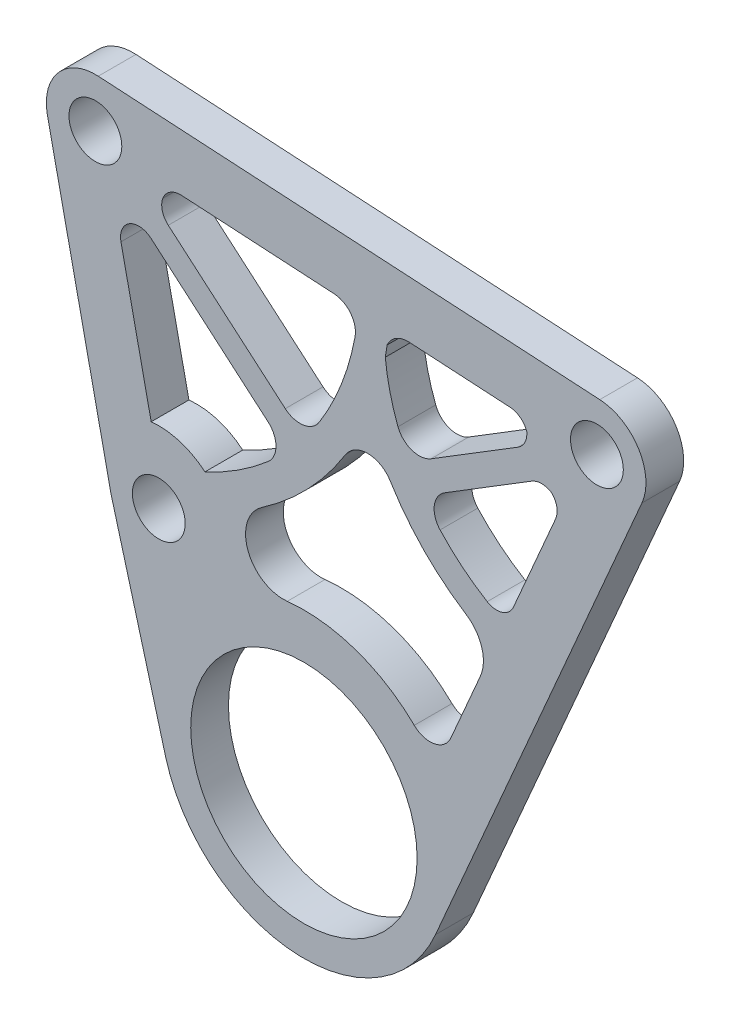
SolidWorks part; units mm, degrees
ref_plane "Front Plane" through (0, 0, 0) normal (0, 0, 1) x (1, 0, 0)
ref_plane "Top Plane" through (0, 0, 0) normal (0, 1, 0) x (1, 0, 0)
ref_plane "Right Plane" through (0, 0, 0) normal (1, 0, 0) x (0, 0, -1)
sketch "Sketch1" plane through (0, 0, 0) normal (0, 0, 1) x (1, 0, 0)
  line L3 (-27.2517, 68.6219) -> (39.2047, 64.735)
  line L4 (-33.9863, 60.7681) -> (-25.5866, 21.66)
  line L7 (-25.5028, 21.3156) -> (-18.3313, -4.9963)
  line L8 (44.7906, 55.6646) -> (17.4374, -7.5457)
  line L9 (-24.3868, 63.4458) -> (35.7559, 59.9282)
  line L10 (-28.4337, 58.7263) -> (-21.3622, 25.8017)
  line L11 (-19.8472, 19.5795) -> (-14.9234, 1.5141)
  line L12 (38.9459, 54.7482) -> (14.9873, -0.6177)
  line L16 (-27.6312, 62.133) -> (0, 0) construction
  circle A0 centre (38.8252, 58.2461) radius 3.5
  circle A1 centre (0, 0) radius 13
  circle A2 centre (-19.2316, 23.0249) radius 3.5
  circle A3 centre (-27.6312, 62.133) radius 3.5
  circle A4 centre (-27.6312, 62.133) radius 6.5
  circle A5 centre (38.8252, 58.2461) radius 6.5
  circle A6 centre (-19.2316, 23.0249) radius 6.5
  circle A7 centre (0, 0) radius 19
  circle A8 centre (0, 0) radius 15
  dimension "D6" = 26
  dimension "D7" = 7
  dimension "D8" = 7
  dimension "D9" = 7
  dimension "D10" = 38
  dimension "D11" = 13
  dimension "D12" = 13
  dimension "D13" = 13
  dimension "D18" = 30
  dimension "D1" = 68
  dimension "D2" = 70
  dimension "D3" = 66.57
  dimension "D4" = 30
  dimension "D5" = 40
  dimension "D14" = 5
  dimension "D15" = 5
  dimension "D16" = 5
  dimension "D17" = 5
extrude "Boss-Extrude2" add sketch "Sketch1" along normal blind 5 contours A5 L3 A4 L9 | A5 L9 A0 L12 | L9 A5 L12 A0 | A3 L16 A4 L9 | L9 A4 L10 A3 | L16 A3 L10 A4 | A6 L10 A4 L4 | A7 L8 A5 L12 | L11 A6 L10 A2 | L10 A6 L11 A2 | A7 L11 A6 L7 | A8 L11 A7 L12 | A7 L16 A8 L12 | L16 A7 L11 A8 | A4 L16 A7 L12 A5 L9 | L16 A4 L10 A6 L11 A7 region at (-23.431, 66.8512, 0) region at (5.8345, 64.2509, 0) region at (43.4213, 62.5812, 0) region at (-27.4669, 41.7122, 0) region at (-23.403, 60.0563, 0) region at (6.823, 41.0913, 0) region at (35.06, 55.9273, 0) region at (-22.9578, 22.1177, 0) region at (-18.5959, 33.0135, 0) region at (-26.8135, 57.1999, 0) region at (29.7136, 26.8388, 0) region at (-20.4113, 10.4427, 0) region at (-15.8467, 28.386, 0) region at (-1.3174, -18.4828, 0) region at (16.1721, 2.9338, 0) region at (-12.1484, 11.0518, 0)
ref_plane "Plane1" through (0, 0, 10.5) normal (0, 0, 1) x (1, 0, 0)
sketch "Sketch6" plane through (0, 0, 0) normal (0, 0, 1) x (1, 0, 0)
  circle A1 centre (0, 0) radius 21
  circle A3 centre (-19.2316, 23.0249) radius 9.5
  circle A5 centre (-27.6312, 62.133) radius 9.5
  circle A7 centre (38.8252, 58.2461) radius 9.5
sketch "Sketch7" plane through (0, 0, 0) normal (0, 0, 1) x (1, 0, 0)
  line L0 (-24.2432, 51.1207) -> (-20.2377, 32.4715)
  line L1 (-27.6312, 62.133) -> (0.6574, 37.8755)
  line L2 (-33.9863, 60.7681) -> (-25.5866, 21.66) construction
  line L3 (-16.231, 60.4645) -> (4.0052, 59.2809)
  line L4 (-27.2517, 68.6219) -> (39.2047, 64.735) construction
  line L5 (33.3489, 48.109) -> (27.7669, 35.2096)
  line L6 (44.7906, 55.6646) -> (17.4374, -7.5457) construction
  line L7 (38.8252, 58.2461) -> (11.4971, 41.4155)
  line L8 (-20.2514, 53.4995) -> (-4.7476, 40.205)
  line L9 (-17.9731, 56.1564) -> (-2.4693, 42.8619)
  line L10 (30.1875, 50.8711) -> (18.6793, 43.7836)
  line L11 (28.3521, 53.8513) -> (16.8439, 46.7637)
  line L12 (13.9417, 58.6998) -> (27.3081, 57.918)
  line L14 (0.6574, 37.8755) -> (1.9745, 36.7461)
  line L15 (23.3701, 25.049) -> (19.4678, 16.0313)
  circle A0 centre (-27.6312, 62.133) radius 9.5 construction
  circle A1 centre (-19.2316, 23.0249) radius 9.5 construction
  circle A2 centre (38.8252, 58.2461) radius 9.5 construction
  arc A6 (-20.2514, 53.4995) -> (-23.0454, 53.8128) centre (-21.8788, 51.6017) ccw
  arc A7 (-23.0454, 53.8128) -> (-24.2432, 51.1207) centre (-21.7989, 51.6457) ccw
  arc A8 (-18.7088, 58.87) -> (-17.9731, 56.1564) centre (-16.3457, 58.0542) ccw
  arc A9 (-16.231, 60.4645) -> (-18.7088, 58.87) centre (-16.3769, 57.9688) ccw
  arc A13 (29.5288, 56.228) -> (27.3081, 57.918) centre (27.1622, 55.4222) ccw
  arc A14 (28.3521, 53.8513) -> (29.5288, 56.228) centre (27.0411, 55.98) ccw
  arc A15 (32.8393, 50.8525) -> (30.1875, 50.8711) centre (31.4985, 48.7424) ccw
  arc A16 (33.3489, 48.109) -> (32.8393, 50.8525) centre (31.0545, 49.1018) ccw
  arc A17 (-13.1084, 30.2883) -> (-4.7382, 35.6584) centre (-27.6312, 62.133) ccw
  arc A18 (2.0256, 43.5461) -> (6.7795, 55.7379) centre (-27.6312, 62.133) ccw
  arc A19 (10.7795, 55.3996) -> (12.4654, 48.2549) centre (38.8252, 58.2461) ccw
  arc A20 (18.0405, 39.2025) -> (24.2876, 34.094) centre (38.8252, 58.2461) ccw
  arc A21 (-13.1084, 30.2883) -> (-20.2377, 32.4715) centre (-19.2316, 23.0249) ccw
  arc A22 (-4.7382, 35.6584) -> (-4.7476, 40.205) centre (-6.7004, 37.9276) ccw
  arc A23 (6.7795, 55.7379) -> (4.0052, 59.2809) centre (3.8301, 56.2861) ccw
  arc A24 (-2.4693, 42.8619) -> (2.0256, 43.5461) centre (-0.5164, 45.1393) ccw
  arc A25 (13.9417, 58.6998) -> (10.7795, 55.3996) centre (13.7664, 55.7027) ccw
  arc A26 (12.4654, 48.2549) -> (16.8439, 46.7637) centre (15.2707, 49.3181) ccw
  arc A27 (18.6793, 43.7836) -> (18.0405, 39.2025) centre (20.2525, 41.2291) ccw
  arc A28 (24.2876, 34.094) -> (27.7669, 35.2096) centre (25.5394, 36.1736) ccw
  arc A29 (-5.5613, 29.9785) -> (5.4838, 41.5323) centre (-27.6312, 62.133) ccw
  arc A33 (-5.5613, 29.9785) -> (-2.2064, 20.8838) centre (-2.7318, 25.8561) ccw
  arc A35 (11.4971, 41.4155) -> (5.4838, 41.5323) centre (8.4557, 39.6835) ccw
  arc A36 (11.442, 41.5088) -> (21.4831, 31.2419) centre (38.8252, 58.2461) ccw
  arc A37 (10.7808, 55.3868) -> (11.0173, 56.9093) centre (-27.6312, 62.133) ccw
  arc A39 (23.3701, 25.049) -> (21.4831, 31.2419) centre (18.7813, 27.0347) ccw
  arc A40 (14.6253, 15.0699) -> (-2.2064, 20.8838) centre (0, 0) ccw
  arc A41 (14.6253, 15.0699) -> (19.4678, 16.0313) centre (16.7146, 17.2227) ccw
  dimension "D10" = 5
  dimension "D11" = 5
  dimension "D12" = 5
  dimension "D13" = 1.75
  dimension "D14" = 1.75
  dimension "D15" = 35
  dimension "D16" = 4
  dimension "D18" = 39
  dimension "D19" = 4
  dimension "D20" = 5
  dimension "D21" = 7
  dimension "D22" = 28.1897
  dimension "D1" = 7.5
  dimension "D2" = 7.5
  dimension "D3" = 7.5
  dimension "D4" = 74.531
  dimension "D5" = 37.265
  dimension "D6" = 69.948
  dimension "D7" = 34.975
  dimension "D8" = 1.75
  dimension "D9" = 1.75
extrude "Cut-Extrude5" cut sketch "Sketch7" against normal through all both and the other way through all contours L8 A22 A17 A21 L0 A7 A6
extrude "Cut-Extrude6" cut sketch "Sketch7<3>" against normal through all both and the other way through all contours L9 A24 A18 A23 L3 A9 A8 | A37 A19 A26 L11 A14 A13 L12 A25 | A20 A28 L5 A16 A15 L10 A27 | A39 A36 L7 A35 A29 A33 region at (-4.4174, 53.1672, 0) region at (25.6513, 42.4005, 0) region at (9.0738, 27.9938, 0) region at (18.7943, 53.5861, 0)
sketch "Sketch7<3>" plane through (0, 0, 0) normal (0, 0, 1) x (1, 0, 0) same geometry as "Sketch7"
